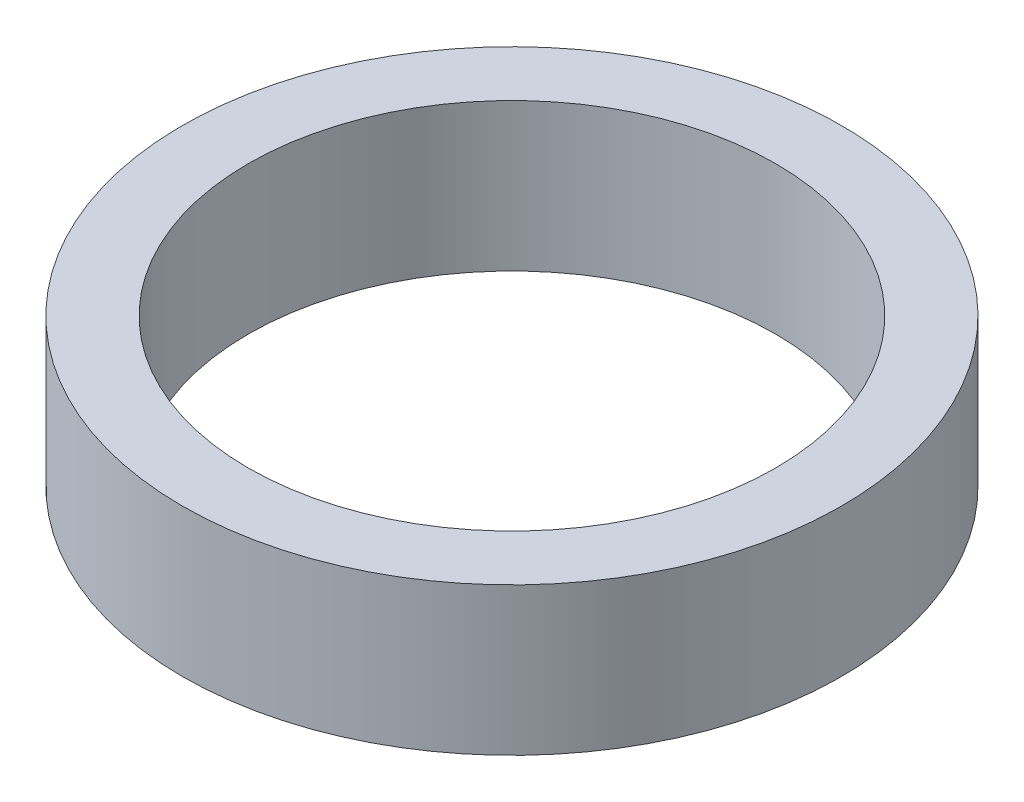
SolidWorks part; units mm, degrees
ref_plane "Front Plane" through (0, 0, 0) normal (0, 0, 1) x (1, 0, 0)
ref_plane "Top Plane" through (0, 0, 0) normal (0, 1, 0) x (1, 0, 0)
ref_plane "Right Plane" through (0, 0, 0) normal (1, 0, 0) x (0, 0, -1)
sketch "Sketch1" plane through (0, 0, 0) normal (0, 1, 0) x (1, 0, 0)
  circle A0 centre (0, 0) radius 62.5
  dimension "FLANGE_OD" = 125
extrude "Boss-Extrude1" add sketch "Sketch1" along normal blind 28
sketch "Sketch2" plane through (0, 0, 0) normal (0, 1, 0) x (1, 0, 0)
  circle A0 centre (0, 0) radius 50
  dimension "BORE_D" = 100
extrude "Cut-Extrude1" cut sketch "Sketch2" along normal through all
sketch "Sketch3" plane through (0, 28, 0) normal (0, 1, 0) x (1, 0, 0)
  circle A0 centre (0, 0) radius 27.3471 construction
  circle A1 centre (-27.3471, 0) radius 1.5357
  dimension "BOLT_D" = 3.0713
  dimension "BOLT_PCD" = 54.6943
extrude "Cut-Extrude2" cut sketch "Sketch3" against normal blind 26.8683 rebuild error yes
pattern_circular "CirPattern1" count 3 over 360 rebuild error yes
